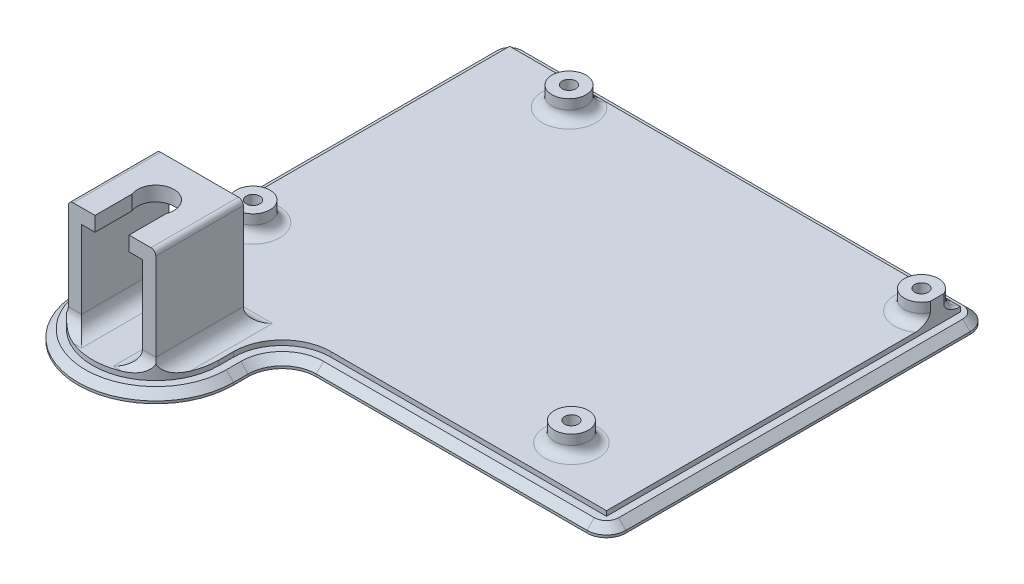
SolidWorks part; units mm, degrees
ref_plane "Спереди" through (0, 0, 0) normal (0, 0, 1) x (1, 0, 0)
ref_plane "Сверху" through (0, 0, 0) normal (0, 1, 0) x (1, 0, 0)
ref_plane "Справа" through (0, 0, 0) normal (1, 0, 0) x (0, 0, -1)
sketch "Эскиз1" plane through (0, 0, 0) normal (0, 1, 0) x (1, 0, 0)
  line L1 (0, 0) -> (92.71, 0)
  line L2 (0, 0) -> (0, 72.77)
  line L3 (0, 72.77) -> (92.71, 72.77)
  line L4 (92.71, 0) -> (92.71, 72.77)
  dimension "D1" = 92.71
  dimension "D2" = 72.77
extrude "Бобышка-Вытянуть1" add sketch "Эскиз1" along normal blind 3
sketch "Эскиз2" plane through (0, 3, 0) normal (0, 1, 0) x (1, 0, 0)
  line L0 (92.71, 66.605) -> (92.71, 69.395)
  line L4 (0, 72.77) -> (0, 0)
  line L5 (0, 0) -> (92.71, 0)
  line L6 (92.71, 0) -> (92.71, 72.77)
  line L7 (92.71, 72.77) -> (0, 72.77)
  line L8 (0, 72.77) -> (0, 0) construction
  line L9 (0, 0) -> (92.71, 0) construction
  line L10 (92.71, 0) -> (92.71, 69.395) construction
  line L11 (92.71, 72.77) -> (0, 72.77) construction
  circle A0 centre (89.5, 68) radius 1.1
  arc A1 (92.71, 69.395) -> (92.71, 66.605) centre (89.5, 68) ccw
  circle A2 centre (17, 68) radius 1.1
  circle A3 centre (17, 68) radius 3.5
  circle A4 centre (5, 15) radius 1.1
  circle A5 centre (5, 15) radius 3.5
  circle A6 centre (77, 8.5) radius 1.1
  circle A7 centre (77, 8.5) radius 3.5
  dimension "D2" = 2.2
  dimension "D3" = 2.2
  dimension "D4" = 2.2
  dimension "D5" = 2.2
  dimension "D6" = 7
  dimension "D7" = 7
  dimension "D8" = 7
  dimension "D9" = 7
  dimension "D10" = 8.5
  dimension "D11" = 68
  dimension "D12" = 89.5
  dimension "D13" = 17
  dimension "D14" = 4.77
  dimension "D15" = 5
  dimension "D16" = 15
  dimension "D17" = 72
  dimension "D1" = 0
extrude "Бобышка-Вытянуть2" add sketch "Эскиз2" along normal blind 4
sketch "Эскиз3" plane through (0, 7, 0) normal (0, 1, 0) x (1, 0, 0)
  circle A0 centre (17, 68) radius 1.4
  circle A1 centre (89.5, 68) radius 1.4
  circle A2 centre (77, 8.5) radius 1.4
  circle A3 centre (5, 15) radius 1.4
  dimension "D1" = 2.8
  dimension "D2" = 2.8
  dimension "D3" = 2.8
  dimension "D4" = 2.8
extrude "Вырез-Вытянуть1" cut sketch "Эскиз3" against normal blind 3
fillet "Скругление1" radius 2 4 edges at (5, 3, -18.5) (77, 3, -12) (86, 3, -68) (17, 3, -71.5)
sketch "Эскиз5" plane through (0, 3, 0) normal (0, 1, 0) x (1, 0, 0)
  circle A0 centre (77, 8.5) radius 1.1 construction
  circle A1 centre (5, 15) radius 1.1 construction
  circle A2 centre (17, 68) radius 1.1 construction
  circle A3 centre (89.5, 68) radius 1.1 construction
  circle A4 centre (77, 8.5) radius 1.1
  circle A5 centre (5, 15) radius 1.1
  circle A6 centre (17, 68) radius 1.1
  circle A7 centre (89.5, 68) radius 1.1
extrude "Вырез-Вытянуть2" cut sketch "Эскиз5" against normal blind 3
ref_plane "Плоскость1" through (0, 22, 0) normal (0, 1, 0) x (1, 0, 0)
sketch "Эскиз8" plane through (0, 22, 0) normal (0, 1, 0) x (1, 0, 0)
  line L0 (0, 12.7087) -> (0, 0) construction
  line L1 (22, -4) -> (4, -4)
  line L2 (22, -4) -> (22, -22)
  line L3 (22, -22) -> (4, -22)
  line L4 (4, -4) -> (4, -22)
  line L5 (22, -4) -> (4, -22) construction
  line L6 (22, -22) -> (4, -4) construction
  line L7 (0, 0) -> (92.71, 0) construction
  circle A0 centre (13, -13) radius 3.75
  circle A1 centre (13, -13) radius 10 construction
  dimension "D1" = 7.5
  dimension "D4" = 20
  dimension "D5" = 13
  dimension "D2" = 18
  dimension "D3" = 18
  dimension "D6" = 13
extrude "Бобышка-Вытянуть4" add sketch "Эскиз8" along normal blind 3 separate body
sketch "Эскиз9" plane through (0, 22, 0) normal (0, -1, 0) x (1, 0, 0)
  line L0 (4, 22) -> (22, 22) construction
  line L1 (19.25, 6.75) -> (6.75, 6.75) construction
  line L2 (19.25, 6.75) -> (19.25, 19.25) construction
  line L3 (19.25, 19.25) -> (6.75, 19.25) construction
  line L4 (6.75, 6.75) -> (6.75, 19.25) construction
  line L5 (19.25, 6.75) -> (6.75, 19.25) construction
  line L6 (19.25, 19.25) -> (6.75, 6.75) construction
  line L7 (4, 4) -> (6.75, 4)
  line L8 (4, 4) -> (4, 22)
  line L9 (4, 22) -> (6.75, 22)
  line L10 (6.75, 4) -> (6.75, 22)
  line L12 (22, 4) -> (19.25, 4)
  line L13 (22, 4) -> (22, 22)
  line L14 (22, 22) -> (19.25, 22)
  line L15 (19.25, 4) -> (19.25, 22)
  point P0 (13, 13)
  dimension "D1" = 12.5
  dimension "D2" = 12.5
extrude "Бобышка-Вытянуть5" add sketch "Эскиз9" along normal blind 19
sketch "Эскиз11" plane through (0, 0, 0) normal (0, -1, 0) x (1, 0, 0)
  line L0 (0, 0) -> (0, 13)
  line L1 (26, 13) -> (26, 0)
  line L2 (0, 0) -> (92.71, 0) construction
  line L3 (0, 0) -> (26, 0)
  arc A1 (26, 13) -> (0, 13) centre (13, 13) ccw
extrude "Бобышка-Вытянуть6" add sketch "Эскиз11" against normal blind 3 contours A1 L0 L3 L1
fillet "Скругление5" radius 10 1 edges at (26, 1.5, 0)
fillet "Скругление6" radius 3 6 edges at (5.375, 3, 4) (20.625, 3, 4) (22, 3, 13) (6.75, 3, 13) (19.25, 3, 13) (4, 3, 13)
fillet "Скругление7" radius 3 2 edges at (19.3154, 3, 22) (6.6846, 3, 22)
sketch "Эскиз6" plane through (0, 0, 0) normal (0, -1, 0) x (1, 0, 0)
  line L8 (95.71, 3) -> (36, 3)
  line L9 (29, 10) -> (29, 13)
  line L10 (-3, 13) -> (-3, -75.77)
  line L11 (-3, -75.77) -> (95.71, -75.77)
  line L12 (0, 13) -> (0, -72.77)
  line L13 (0, -72.77) -> (92.71, -72.77)
  line L14 (92.71, -72.77) -> (92.71, 0)
  line L15 (92.71, 0) -> (36, 0)
  line L16 (0, 13) -> (0, -72.77)
  line L17 (0, -72.77) -> (92.71, -72.77)
  line L18 (92.71, -72.77) -> (92.71, 0)
  line L19 (92.71, 0) -> (36, 0)
  line L20 (95.71, -75.77) -> (95.71, 3)
  line L21 (26, 10) -> (26, 13)
  line L22 (26, 10) -> (26, 13)
  arc A0 (29, 10) -> (36, 3) centre (36, 10) ccw
  arc A1 (29, 13) -> (-3, 13) centre (13, 13) ccw
  arc A2 (26, 10) -> (36, 0) centre (36, 10) ccw
  arc A3 (26, 10) -> (36, 0) centre (36, 10) ccw
  arc A4 (26, 13) -> (0, 13) centre (13, 13) ccw
  arc A5 (26, 13) -> (0, 13) centre (13, 13) ccw
  dimension "D1" = 3
  dimension "D5" = 0
extrude "Бобышка-Вытянуть3" add sketch "Эскиз6" against normal blind 2
fillet "Скругление8" radius 4 3 edges at (-3, 1, -75.77) (95.71, 1, -75.77) (95.71, 1, 3)
chamfer "Фаска1" distance 1.5 angle 45 10 edges at (63.855, 2, 3) (31.0503, 2, 5.0503) (29, 2, 11.5) (13, 2, 29) (-3, 2, -29.385) (95.71, 2, -36.385) (46.355, 2, -75.77) (94.5384, 2, 1.8284) (94.5384, 2, -74.5984) (-1.8284, 2, -74.5984)
fillet "Скругление9" radius 1 2 edges at (22, 25, 13) (4, 25, 13)
sketch "Эскиз12" plane through (0, 25, 0) normal (0, 1, 0) x (1, 0, 0)
  line L3 (9.5, -14.3463) -> (9.5, -23.4708)
  line L4 (9.5, -23.4708) -> (16.5, -23.4708)
  line L5 (16.5, -23.4708) -> (16.5, -14.3463)
  line L6 (13, -16.75) -> (13, -25.1234) construction
  arc A2 (16.5, -14.3463) -> (9.5, -14.3463) centre (13, -13) ccw
  dimension "D1" = 3.5
  dimension "D2" = 3.5
extrude "Вырез-Вытянуть3" cut sketch "Эскиз12" against normal blind 10 contours L4 L5 A2 L3
